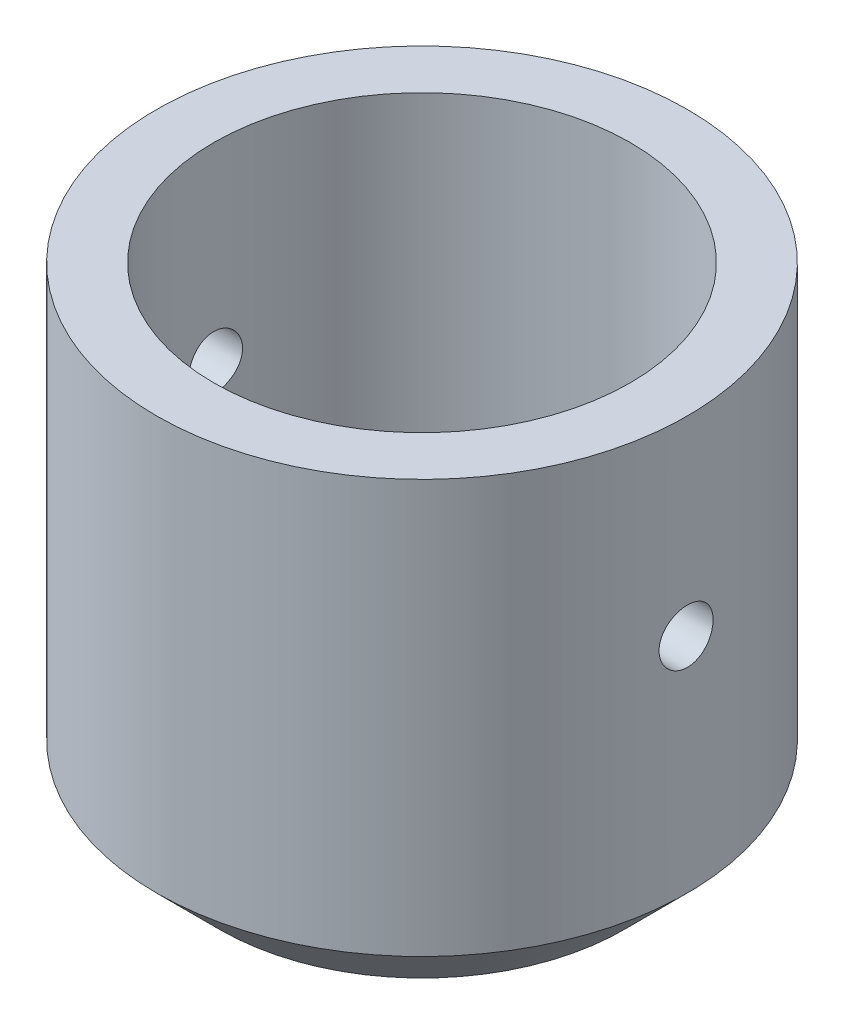
SolidWorks part; units mm, degrees
ref_plane "Front Plane" through (0, 0, 0) normal (0, 0, 1) x (1, 0, 0)
ref_plane "Top Plane" through (0, 0, 0) normal (0, 1, 0) x (1, 0, 0)
ref_plane "Right Plane" through (0, 0, 0) normal (1, 0, 0) x (0, 0, -1)
sketch "Sketch1" plane through (0, 0, 0) normal (0, 1, 0) x (1, 0, 0)
  circle A0 centre (0, 0) radius 6.35 construction
  circle A1 centre (0, 0) radius 8.35
  dimension "D1" = 12.7
  dimension "D2" = 2
extrude "Boss-Extrude1" add sketch "Sketch1" along normal blind 15
sketch "Sketch2" plane through (0, 15, 0) normal (0, 1, 0) x (1, 0, 0)
  circle A0 centre (0, 0) radius 6.55
  dimension "D1" = 13.1
extrude "Cut-Extrude1" cut sketch "Sketch2" against normal offset from surface (12 mm away) 3 up to face at (0, 0, 8.35)
sketch "Sketch3" plane through (0, 0, 0) normal (1, 0, 0) x (0, 0, -1)
  line L0 (0, 15) -> (0, 9) construction
  line L1 (6.55, 15) -> (-6.55, 15) construction
  circle A0 centre (0, 9) radius 0.85
  dimension "D2" = 1.7
  dimension "D1" = 6
extrude "Cut-Extrude2" cut sketch "Sketch3" against normal through all both and the other way through all
sketch "Sketch4" plane through (0, 0, 0) normal (0, -1, 0) x (1, 0, 0)
  circle A0 centre (0, 0) radius 4.15
  dimension "D1" = 8.3
extrude "Cut-Extrude3" cut sketch "Sketch4" against normal through all
chamfer "Chamfer1" distance 2 angle 45 1 edges at (0, 0, 8.35)
